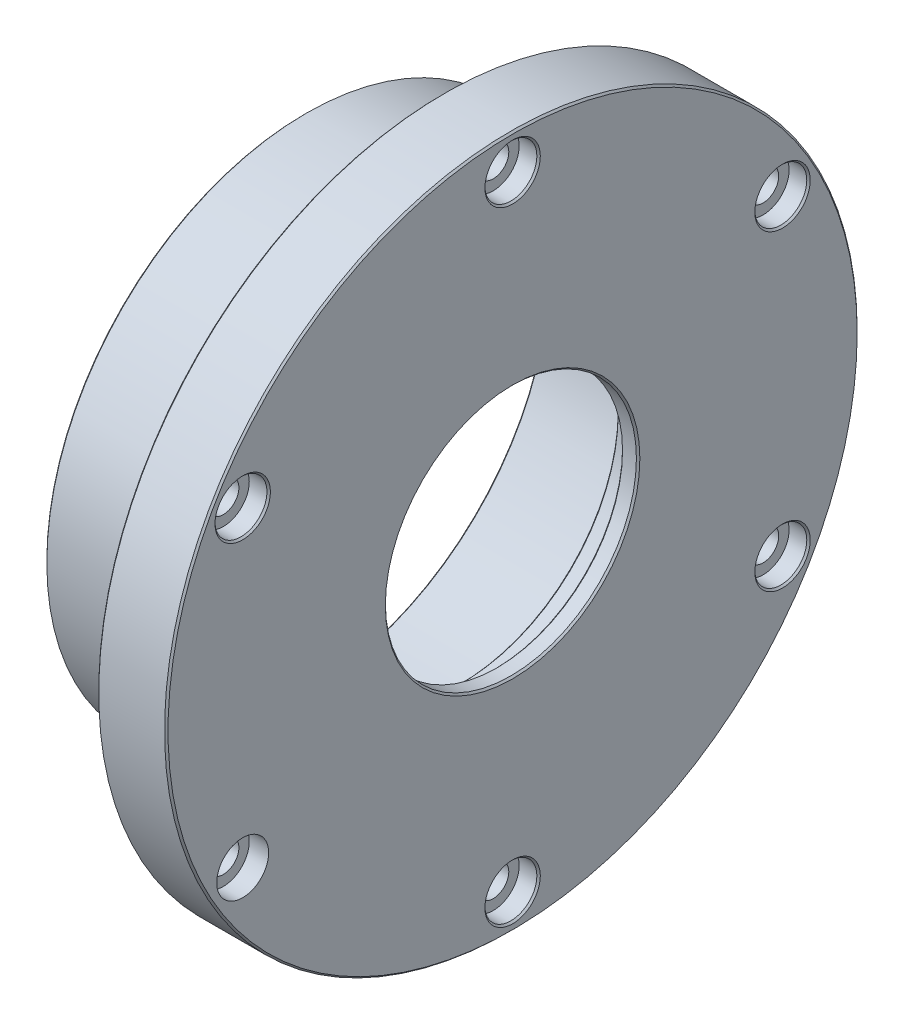
SolidWorks part; units mm, degrees
ref_plane "Front Plane" through (0, 0, 0) normal (0, 0, 1) x (1, 0, 0)
ref_plane "Top Plane" through (0, 0, 0) normal (0, 1, 0) x (1, 0, 0)
ref_plane "Right Plane" through (0, 0, 0) normal (1, 0, 0) x (0, 0, -1)
sketch "Sketch1" plane through (0, 0, 0) normal (0, 0, 1) x (1, 0, 0)
  line L0 (-15.2619, -33.1832) -> (53.5176, -33.1832)
  line L1 (22.9387, 66.8168) -> (42.9387, 66.8168)
  line L2 (-17.0613, 41.8168) -> (-17.0613, 36.8168)
  line L3 (37.9387, 3.0668) -> (42.9387, 3.0668)
  line L5 (42.9387, 66.8168) -> (42.9387, 3.0668)
  line L16 (-17.0613, 41.8168) -> (22.9387, 41.8168)
  line L17 (22.9387, 66.8168) -> (22.9387, 41.8168)
  line L20 (-17.0613, 36.8168) -> (21.9387, 36.8168)
  line L21 (21.9387, 26.8168) -> (21.9387, 36.8168)
  line L22 (21.9387, 26.8168) -> (27.9387, 26.8168)
  line L25 (37.9387, 11.8168) -> (37.9387, 3.0668)
  line L32 (37.9387, 11.8168) -> (27.9387, 11.8168)
  line L33 (27.9387, 26.8168) -> (27.9387, 11.8168)
  dimension "D1" = 63.75
  dimension "D2" = 40
  dimension "D3" = 36.25
  dimension "D4" = 39
  dimension "D5" = 10
  dimension "D6" = 5
  dimension "D7" = 20
  dimension "D8" = 5
  dimension "D9" = 15
  dimension "D11" = 10
revolve "Revolve1" add sketch "Sketch1" angle 360 about L0 region at (28.861, 39.3406, 0)
sketch "Sketch2" plane through (42.9387, 0, 0) normal (1, 0, 0) x (0, 0, -1)
  line L0 (0, -33.1832) -> (0, 56.8168)
  line L1 (0, -33.1832) -> (77.9423, 11.8168)
  line L2 (0, -33.1832) -> (77.9423, -78.1832)
  line L3 (0, -33.1832) -> (0, -123.1832)
  line L4 (0, -33.1832) -> (-77.9423, -78.1832)
  line L5 (0, -33.1832) -> (-77.9423, 11.8168)
  point P6 (0, 56.8168)
  point P9 (0, -33.1832)
  point P24 (-77.9423, 11.8168)
  point P27 (-77.9423, -78.1832)
  point P30 (0, -123.1832)
  point P33 (77.9423, -78.1832)
  point P36 (77.9423, 11.8168)
  dimension "D1" = 90
  dimension "D2" = 6
hole_wizard "CBORE for M8 Hex Socket Thin Head Cap Screw1" positions "Sketch2" profile "Sketch3" counterbore size "M8" standard "DIN"
sketch "Sketch3" plane through (42.9387, 11.8168, -77.9423) normal (0, 1, 0) x (0, 0, -1)
  line L0 (0, 0) -> (0, 22.7039)
  line L1 (0, 22.7039) -> (4.5, 20)
  line L2 (4.5, 20) -> (4.5, 5.6)
  line L3 (4.5, 5.6) -> (7.5, 5.6)
  line L4 (7.5, 5.6) -> (7.5, 0)
  line L5 (7.5, 0) -> (0, 0)
  line L10 (0, 22.7039) -> (-4.5, 20) construction
  line L11 (0, -6.35) -> (0, 107.95) construction
  dimension "Hole Dia." = 9
  dimension "Hole Depth" = 20
  dimension "C'Bore Dia." = 15
  dimension "C'Bore Depth" = 5.6
  dimension "Drill Angle" = 118
chamfer "Chamfer1" distance 0.5 angle 45 19 edges at (22.9387, -33.1832, 100) (-17.0613, -33.1832, 75) (22.9387, -123.1832, -4.5) (22.9387, -78.1832, -82.4423) (22.9387, 11.8168, -82.4423) (22.9387, 56.8168, -4.5) (22.9387, 11.8168, 73.4423) (22.9387, -78.1832, 73.4423) (42.9387, -123.1832, -7.5) (42.9387, -78.1832, -85.4423) (42.9387, 11.8168, -85.4423) (42.9387, 56.8168, -7.5) (42.9387, 11.8168, 70.4423) (-17.0613, -33.1832, 70) (42.9387, -33.1832, 36.25) (42.9387, -33.1832, 100) (37.9387, -33.1832, 36.25) (27.9387, -33.1832, 45) (21.9387, -33.1832, 60)
